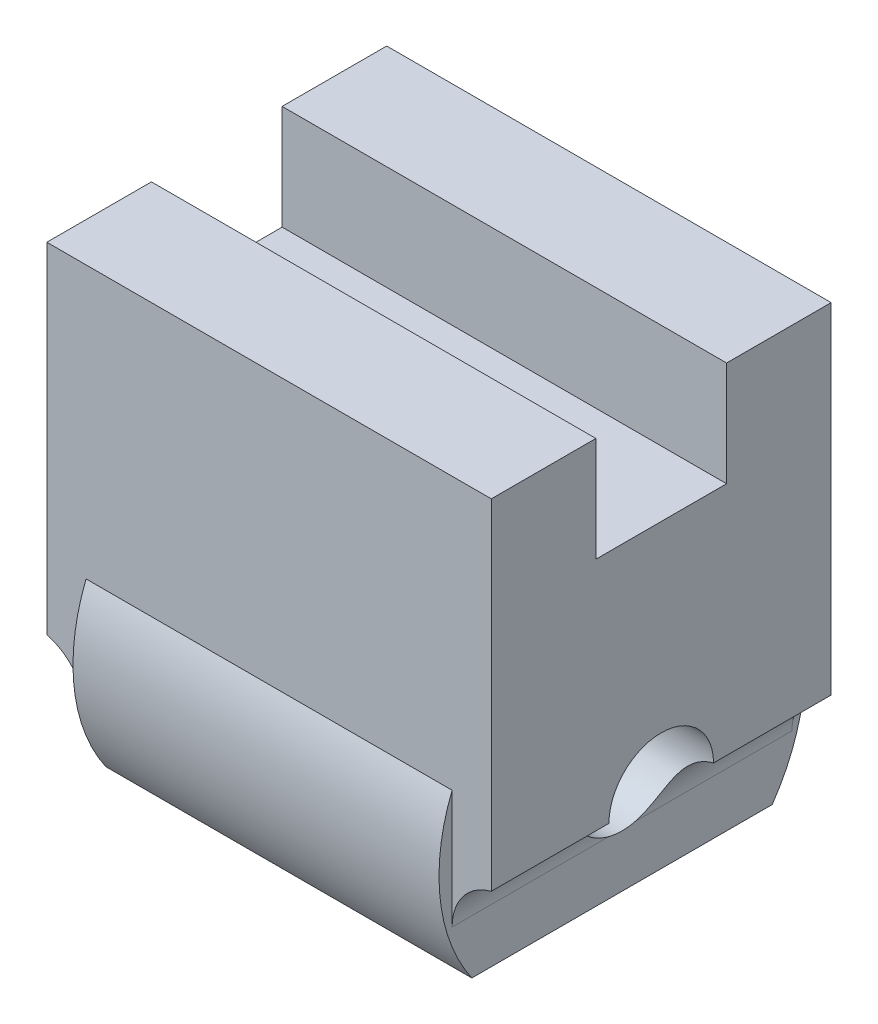
SolidWorks part; units mm, degrees
ref_plane "Plan de face" through (0, 0, 0) normal (0, 0, 1) x (1, 0, 0)
ref_plane "Plan de dessus" through (0, 0, 0) normal (0, 1, 0) x (1, 0, 0)
ref_plane "Plan de droite" through (0, 0, 0) normal (1, 0, 0) x (0, 0, -1)
sketch "Esquisse4" plane through (0, 0, 0) normal (1, 0, 0) x (0, 0, -1)
  circle A0 centre (0, 70) radius 70
  circle A1 centre (0, 70) radius 20
  dimension "D1" = 140
  dimension "D2" = 40
extrude "Boss.-Extru.1" add sketch "Esquisse4" along normal mid plane 140
ref_plane "Plan1" through (0, 70, 0) normal (0, -1, 0) x (-1, 0, 0)
sketch "Esquisse8" plane through (0, 70, 0) normal (0, -1, 0) x (-1, 0, 0)
  line L1 (85, -65) -> (-85, -65)
  line L2 (85, -65) -> (85, 65)
  line L3 (85, 65) -> (-85, 65)
  line L4 (-85, -65) -> (-85, 65)
  line L5 (85, -65) -> (-85, 65) construction
  line L6 (85, 65) -> (-85, -65) construction
  point P1 (0, 0)
  dimension "D1" = 170
  dimension "D2" = 130
extrude "Boss.-Extru.2" add sketch "Esquisse8" against normal blind 130
sketch "Esquisse9" plane through (85, 0, 0) normal (1, 0, 0) x (0, 0, -1)
  line L0 (65, 200) -> (-65, 200) construction
  line L1 (-25, 240) -> (25, 240)
  line L2 (-25, 240) -> (-25, 160)
  line L3 (-25, 160) -> (25, 160)
  line L4 (25, 240) -> (25, 160)
  line L5 (-25, 240) -> (25, 160) construction
  line L6 (-25, 160) -> (25, 240) construction
  point P0 (0, 200)
  dimension "D1" = 80
  dimension "D2" = 50
extrude "Enlèv. mat.-Extru.1" cut sketch "Esquisse9" against normal through all both and the other way through all
sketch "Esquisse10" plane through (70, 0, 0) normal (1, 0, 0) x (0, 0, -1)
  circle A0 centre (0, 70) radius 20
extrude "Enlèv. mat.-Extru.2" cut sketch "Esquisse10" against normal through all both and the other way through all
fillet "Congé2" radius 20 2 edges at (-70, 70, -42.5) (-70, 70, 42.5)
fillet "Congé3" radius 20 2 edges at (70, 70, 42.5) (70, 70, -42.5)
sketch "Esquisse11" plane through (0, 0, 0) normal (1, 0, 0) x (0, 0, -1)
  line L0 (0, 50) -> (0, 30) construction
  line L2 (80.7148, 30) -> (-85.4627, 30)
  line L3 (80.7148, 30) -> (80.7148, -12.8712)
  line L4 (80.7148, -12.8712) -> (-85.4627, -12.8712)
  line L5 (-85.4627, 30) -> (-85.4627, -12.8712)
  arc A0 (-5, 50.6351) -> (5, 50.6351) centre (0, 70) ccw construction
  dimension "D1" = 20
extrude "Enlèv. mat.-Extru.3" cut sketch "Esquisse11" against normal through all both and the other way through all
